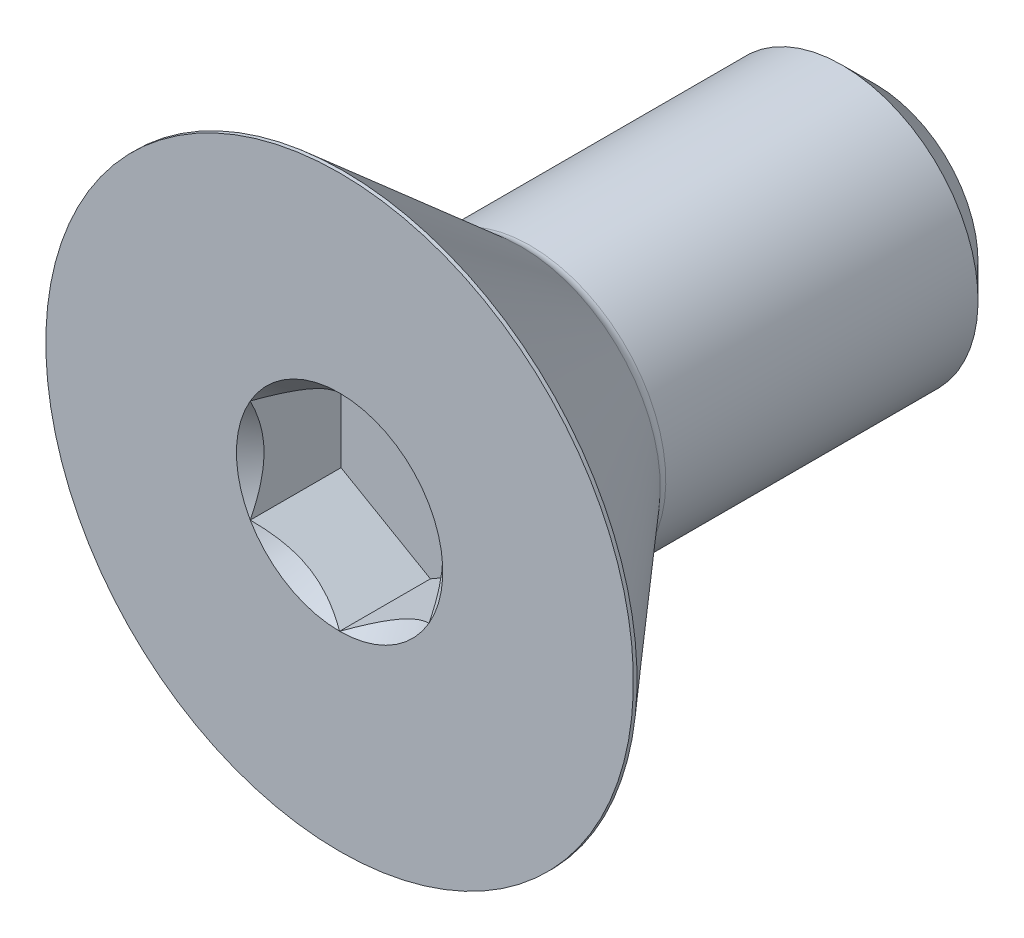
SolidWorks part; units mm, degrees
material "Cast Alloy Steel"
ref_plane "Front Plane" through (0, 0, 0) normal (0, 0, 1) x (1, 0, 0)
ref_plane "Top Plane" through (0, 0, 0) normal (0, 1, 0) x (1, 0, 0)
ref_plane "Right Plane" through (0, 0, 0) normal (1, 0, 0) x (0, 0, -1)
sketch "Sketch1" plane through (0, 0, 0) normal (1, 0, 0) x (0, 0, -1)
  line L0 (-4.7625, 0) -> (4.7625, 0) construction
  line L1 (-4.7625, 0) -> (-4.7625, 5.2197)
  line L2 (-4.7625, 5.2197) -> (-4.698, 5.2197)
  line L3 (-4.698, 5.2197) -> (-1.5367, 2.4716)
  line L4 (-4.698, -5.2197) -> (-1.5367, -2.4716)
  line L5 (4.7625, 0) -> (4.7625, 2.413)
  line L6 (4.7625, 2.413) -> (-1.5367, 2.413)
  line L7 (4.1672, 2.413) -> (4.7625, 1.8177)
  line L8 (4.7129, 2.4989) -> (5.1098, 1.8115) construction
  line L9 (5.1098, 1.8115) -> (5.5066, 2.4989) construction
  line L10 (5.5066, 2.4989) -> (4.7129, 2.4989) construction
  line L11 (4.7377, 2.456) -> (5.4818, 2.456)
  line L12 (5.4818, 2.456) -> (5.1594, 1.8974)
  line L13 (5.1594, 1.8974) -> (5.0602, 1.8974)
  line L14 (5.0602, 1.8974) -> (4.7377, 2.456)
  line L15 (5.1098, 1.8974) -> (5.1098, 1.8115) construction
  line L16 (4.7625, 2.413) -> (5.457, 2.413) construction
  line L17 (5.1098, 2.4989) -> (5.1098, 2.413) construction
  line L18 (4.7625, -2.413) -> (-1.5367, -2.413)
  arc A0 (-1.5367, 2.4716) -> (-1.3799, 2.413) centre (-1.3799, 2.6521) ccw
  point P2 (0, 0)
  point P23 (-3.1496, 0)
  point P27 (5.1098, 2.456)
  point P30 (3.5719, -2.413)
  point P31 (-1.5367, 5.2197)
  point P34 (-4.698, -5.2197)
  dimension "Length" = 9.525
  dimension "Head Height" = 3.2258
  dimension "Head Diameter" = 10.4394
  dimension "Countersink Angle" = 82
  dimension "Screw Size Decimal Equivalent" = 4.826
  dimension "Pitch" = 0.7937
  dimension "D4" = 0.0992
  dimension "D3" = 45
  dimension "D5" = 0.5953
  dimension "D6" = 1.6129
  dimension "D1" = 1.1906
  dimension "D7" = 0.0645
sketch "Sketch8" plane through (0, 0, 0) normal (0, 0, 1) x (1, 0, 0)
  line L1 (0, 1.8331) -> (-1.5875, 0.9165)
  line L2 (-1.5875, 0.9165) -> (-1.5875, -0.9165)
  line L3 (-1.5875, -0.9165) -> (0, -1.8331)
  line L4 (0, -1.8331) -> (1.5875, -0.9165)
  line L5 (1.5875, -0.9165) -> (1.5875, 0.9165)
  line L6 (1.5875, 0.9165) -> (0, 1.8331)
  circle A0 centre (0, 0) radius 1.5875 construction
  dimension "Drive Size" = 3.175
sketch "Sketch2" plane through (0, 0, 0) normal (1, 0, 0) x (0, 0, -1)
  line L0 (-4.698, 5.2197) -> (-1.5367, 2.4716) construction
  line L1 (-4.7625, 0) -> (-4.7625, 5.2197) construction
  line L2 (-4.698, 5.2197) -> (-1.5367, 2.4716)
  line L3 (-4.7625, 0) -> (-4.7625, 5.2197)
  line L4 (-4.7625, 5.2197) -> (-4.698, 5.2197) construction
  line L5 (-4.7625, 5.2197) -> (-4.698, 5.2197)
  line L6 (-1.3799, 2.413) -> (4.1672, 2.413)
  line L7 (4.1672, 2.413) -> (4.7625, 1.8177)
  line L8 (4.7625, 1.8177) -> (4.7625, 0)
  line L9 (4.7625, 0) -> (-4.7625, 0)
  arc A0 (-1.5367, 2.4716) -> (-1.3799, 2.413) centre (-1.3799, 2.6521) ccw construction
  arc A1 (-1.5367, 2.4716) -> (-1.3799, 2.413) centre (-1.3799, 2.6521) ccw
revolve "Revolve1" add sketch "Sketch2" angle 360 about L9
sketch "Sketch9" plane through (0, 0, 4.7625) normal (0, 0, 1) x (1, 0, 0)
  line L0 (1.5875, -0.9165) -> (1.5875, 0.9165) construction
  line L1 (0, -1.8331) -> (1.5875, -0.9165) construction
  line L2 (-1.5875, -0.9165) -> (0, -1.8331) construction
  line L3 (-1.5875, 0.9165) -> (-1.5875, -0.9165) construction
  line L4 (0, 1.8331) -> (-1.5875, 0.9165) construction
  line L5 (1.5875, 0.9165) -> (0, 1.8331) construction
  line L6 (1.5875, -0.9165) -> (1.5875, 0.9165)
  line L7 (0, -1.8331) -> (1.5875, -0.9165)
  line L8 (-1.5875, -0.9165) -> (0, -1.8331)
  line L9 (-1.5875, 0.9165) -> (-1.5875, -0.9165)
  line L10 (0, 1.8331) -> (-1.5875, 0.9165)
  line L11 (1.5875, 0.9165) -> (0, 1.8331)
sketch "Sketch10" plane through (0, 0, 4.7625) normal (0, 0, 1) x (1, 0, 0)
  circle A0 centre (0, 0) radius 1.8331
extrude "Cut-Extrude2" cut sketch "Sketch10" against normal up to vertex (1.6129 mm away) draft 45 up to point (0, 0, 3.1496)
extrude "Cut-Extrude1" cut sketch "Sketch9" against normal up to vertex (1.6129 mm away) up to point (0, 0, 3.1496)
ref_plane "Plane1" [suppressed] through (0, 0, 1.3799) normal (0, 0, 1) x (1, 0, 0)
split "Split1" [suppressed] bodies to split 111
sketch "Sketch3" [suppressed] plane through (0, 0, -4.7625) normal (0, 0, -1) x (-1, 0, 0)
  circle A0 centre (0, 0) radius 2.413 construction
  circle A1 centre (0, 0) radius 2.413
curve "Helix/Spiral1" [suppressed] pitch 0.7937 height 9.525 turns 12
sketch "Sketch4" [suppressed] plane through (0, 0, 0) normal (1, 0, 0) x (0, 0, -1)
  line L0 (4.7377, 2.456) -> (5.4818, 2.456) construction
  line L1 (5.0602, 1.8974) -> (4.7377, 2.456) construction
  line L2 (5.1594, 1.8974) -> (5.0602, 1.8974) construction
  line L3 (5.4818, 2.456) -> (5.1594, 1.8974) construction
  line L4 (4.7377, 2.456) -> (5.4818, 2.456)
  line L5 (5.0602, 1.8974) -> (4.7377, 2.456)
  line L6 (5.1594, 1.8974) -> (5.0602, 1.8974)
  line L7 (5.4818, 2.456) -> (5.1594, 1.8974)
sweep "Cut-Sweep1" [suppressed] cut profiles "Sketch4" path "Helix/Spiral1"
sketch "Sketch7" [suppressed] plane through (0, 0, 1.3799) normal (0, 0, 1) x (1, 0, 0)
  circle A0 centre (0, 0) radius 2.413
extrude "Boss-Extrude2" [suppressed] add sketch "Sketch7" against normal up to next draft 20
equation "\"D4@Sketch1\" = \"Pitch@Sketch1\" / 8"
equation "\"D5@Sketch1\"=\"Pitch@Sketch1\"*0.75"
equation "\"D4@Helix/Spiral1\"=\"Pitch@Sketch1\""
equation "\"D3@Helix/Spiral1\"=\"Length@Sketch1\""
equation "\"D6@Sketch1\"=\"Head Height@Sketch1\"/2"
equation "\"D1@Sketch1\"=\"Pitch@Sketch1\"*1.5"
equation "\"D7@Sketch1\"=\"Head Height@Sketch1\"*0.02"
